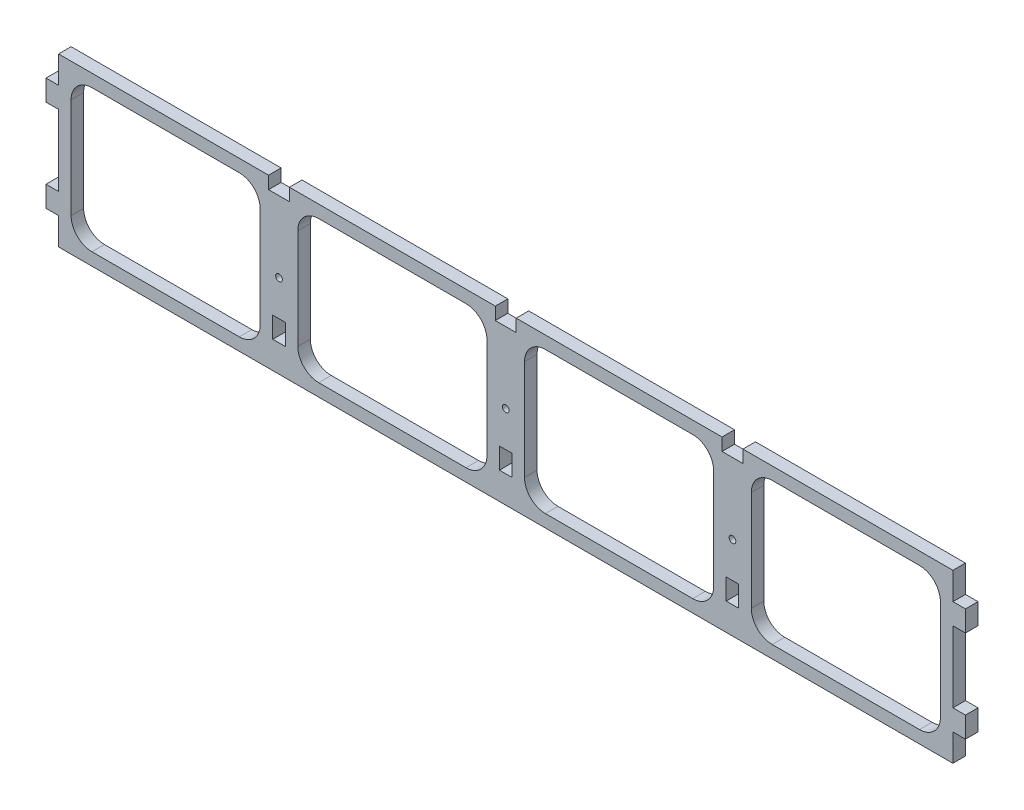
SolidWorks part; units mm, degrees
ref_plane "Front Plane" through (0, 0, 0) normal (0, 0, 1) x (1, 0, 0)
ref_plane "Top Plane" through (0, 0, 0) normal (0, 1, 0) x (1, 0, 0)
ref_plane "Right Plane" through (0, 0, 0) normal (1, 0, 0) x (0, 0, -1)
sketch "Sketch1" plane through (0, 0, 0) normal (0, 0, 1) x (1, 0, 0)
  line L1 (-214, -40) -> (214, -40)
  line L2 (-214, -40) -> (-214, 40)
  line L3 (-214, 40) -> (214, 40)
  line L4 (214, -40) -> (214, 40)
  line L5 (-214, -40) -> (214, 40) construction
  line L6 (-214, 40) -> (214, -40) construction
  point P0 (0, 0)
  dimension "D1" = 428
  dimension "D2" = 80
extrude "Boss-Extrude1" add sketch "Sketch1" along normal blind 6
sketch "Sketch2" plane through (0, 0, 6) normal (0, 0, 1) x (1, 0, 0)
  line L0 (-117.5, -40) -> (-117.5, -27) construction
  line L1 (-208, 40) -> (-208, -40) construction
  line L2 (-214, -34) -> (214, -34) construction
  line L3 (-214, -40) -> (214, -40) construction
  line L8 (214, -40) -> (214, 40)
  line L9 (214, 40) -> (-214, 40)
  line L10 (-214, 40) -> (-214, -40)
  line L11 (-214, -40) -> (214, -40)
  line L12 (214, -40) -> (214, 40) construction
  line L13 (214, 40) -> (-214, 40)
  line L14 (-214, 40) -> (-214, -40) construction
  line L15 (-208, -40) -> (214, -40) construction
  line L16 (-111.5, -40) -> (-111.5, -27) construction
  line L17 (-111.5, -40) -> (-111.5, -27) construction
  line L18 (-117.5, -24) -> (-117.5, 24)
  line L19 (-198, -34) -> (-127.5, -34)
  line L20 (-208, 24) -> (-208, -24)
  line L21 (-127.5, 34) -> (-198, 34)
  arc A0 (-198, 34) -> (-208, 24) centre (-198, 24) ccw
  arc A1 (-127.5, 34) -> (-117.5, 24) centre (-127.5, 24) cw
  arc A2 (-117.5, -24) -> (-127.5, -34) centre (-127.5, -24) cw
  arc A3 (-198, -34) -> (-208, -24) centre (-198, -24) cw
  point P7 (0, 0)
  point P14 (0, 0)
  point P18 (0, 0)
  dimension "D6" = 10
  dimension "D5" = 6
  dimension "D1" = 0
  dimension "D2" = 6
  dimension "D3" = 6
  dimension "D4" = 6
extrude "Cut-Extrude1" cut sketch "Sketch2" against normal up to next contours L18 L21 L20 L19 region at (-162.75, 0, 6)
pattern_linear "LPattern1" count 4 spacing 108.5 along (1, 0, 0) of "Cut-Extrude1"
sketch "Sketch3" plane through (0, 0, 0) normal (0, 0, -1) x (-1, 0, 0)
  line L8 (-111.5, -27) -> (-111.5, -17) construction
  line L9 (-111.5, -17) -> (-105.5, -17) construction
  line L10 (-105.5, -17) -> (-105.5, -27) construction
  line L11 (-105.5, -27) -> (-111.5, -27) construction
  line L24 (-111.5, -27) -> (-111.5, -17)
  line L25 (-111.5, -17) -> (-105.5, -17)
  line L26 (-105.5, -17) -> (-105.5, -27)
  line L27 (-105.5, -27) -> (-111.5, -27)
  line L44 (-3, -27) -> (-3, -17) construction
  line L45 (-3, -17) -> (3, -17) construction
  line L46 (3, -17) -> (3, -27) construction
  line L47 (3, -27) -> (-3, -27) construction
  line L52 (-3, -27) -> (-3, -17)
  line L53 (-3, -17) -> (3, -17)
  line L54 (3, -17) -> (3, -27)
  line L55 (3, -27) -> (-3, -27)
  line L60 (105.5, -27) -> (105.5, -17) construction
  line L61 (105.5, -17) -> (111.5, -17) construction
  line L62 (111.5, -17) -> (111.5, -27) construction
  line L63 (111.5, -27) -> (105.5, -27) construction
  line L68 (105.5, -27) -> (105.5, -17)
  line L69 (105.5, -17) -> (111.5, -17)
  line L70 (111.5, -17) -> (111.5, -27)
  line L71 (111.5, -27) -> (105.5, -27)
  circle A3 centre (108.5, 0) radius 1.6 construction
  circle A4 centre (0, 0) radius 1.6 construction
  circle A5 centre (-108.5, 0) radius 1.6 construction
  circle A6 centre (108.5, 0) radius 1.6
  circle A7 centre (0, 0) radius 1.6
  circle A8 centre (-108.5, 0) radius 1.6
extrude "Cut-Extrude2" cut sketch "Sketch3" against normal through all
sketch "Sketch4" plane through (0, 0, 0) normal (0, 0, -1) x (-1, 0, 0)
  line L0 (-111.5, 17) -> (-214, 17) construction
  line L1 (-214, -40) -> (-214, 40) construction
  line L2 (-108.5, 0) -> (-214, 0) construction
  line L3 (-220, 21.3321) -> (-220, 40) construction
  line L4 (-214, 17) -> (-220, 17)
  line L5 (-214, 17) -> (-214, 27)
  line L6 (-214, 27) -> (-220, 27)
  line L7 (-220, 17) -> (-220, 27)
  line L9 (-220, -17) -> (-220, -27)
  line L10 (-214, -27) -> (-220, -27)
  line L11 (-214, -17) -> (-214, -27)
  line L12 (-214, -17) -> (-220, -17)
  line L13 (0, 0) -> (0, 40) construction
  line L14 (-214, 40) -> (214, 40) construction
  line L15 (214, -17) -> (220, -17)
  line L16 (214, -17) -> (214, -27)
  line L17 (214, -27) -> (220, -27)
  line L18 (220, -17) -> (220, -27)
  line L19 (220, 17) -> (220, 27)
  line L20 (214, 27) -> (220, 27)
  line L21 (214, 17) -> (214, 27)
  line L22 (214, 17) -> (220, 17)
  dimension "D1" = 34
  dimension "D2" = 10
extrude "Boss-Extrude2" add sketch "Sketch4" against normal blind 6
sketch "Sketch5" plane through (0, 40, 0) normal (0, 1, 0) x (1, 0, 0)
  line L0 (214, -6) -> (-214, -6) construction
  line L1 (-113.5, 0) -> (-103.5, 0)
  line L2 (-113.5, 0) -> (-113.5, -6)
  line L3 (-113.5, -6) -> (-103.5, -6)
  line L4 (-103.5, 0) -> (-103.5, -6)
  line L5 (-113.5, 0) -> (-103.5, -6) construction
  line L6 (-113.5, -6) -> (-103.5, 0) construction
  line L7 (-103.5, -6) -> (-103.5, 0) construction
  line L8 (5, -6) -> (5, 0) construction
  line L9 (-5, 0) -> (5, 0)
  line L10 (-5, 0) -> (-5, -6)
  line L11 (-5, -6) -> (5, -6)
  line L12 (5, 0) -> (5, -6)
  line L13 (-5, 0) -> (5, -6) construction
  line L14 (-5, -6) -> (5, 0) construction
  line L15 (113.5, -6) -> (113.5, 0) construction
  line L16 (103.5, 0) -> (113.5, 0)
  line L17 (103.5, 0) -> (103.5, -6)
  line L18 (103.5, -6) -> (113.5, -6)
  line L19 (113.5, 0) -> (113.5, -6)
  line L20 (103.5, 0) -> (113.5, -6) construction
  line L21 (103.5, -6) -> (113.5, 0) construction
  point P0 (-108.5, -3)
  point P10 (0, -3)
  point P18 (108.5, -3)
extrude "Cut-Extrude3" cut sketch "Sketch5" against normal blind 6
